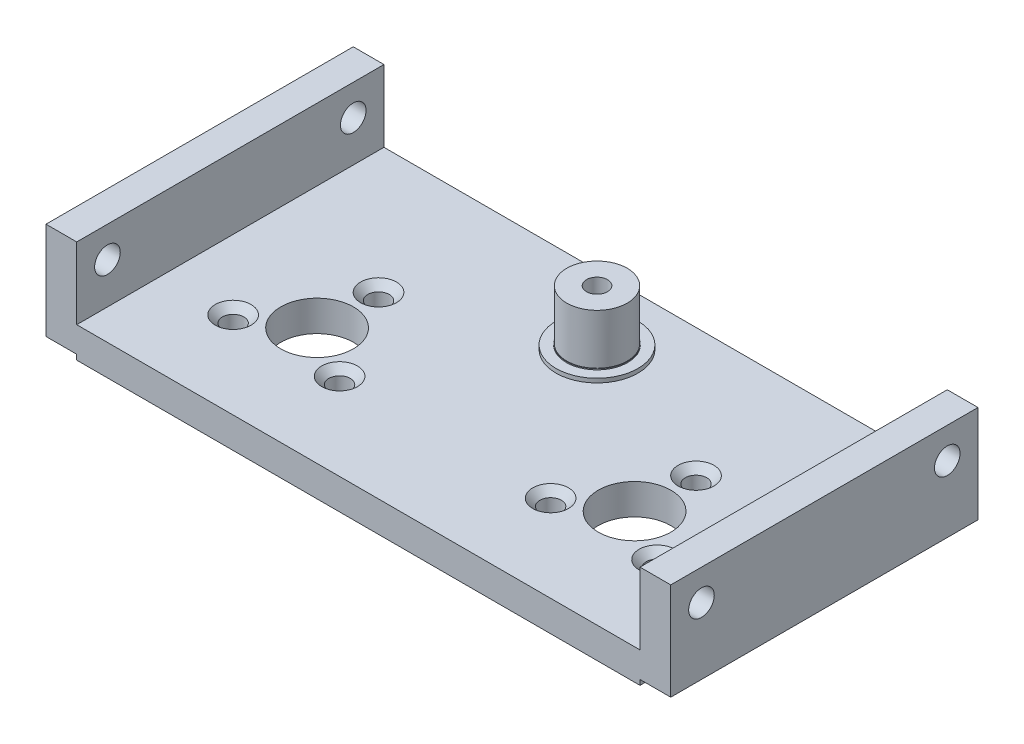
SolidWorks part; units mm, degrees
material "6061 Alloy"
ref_plane "Front Plane" through (0, 0, 0) normal (0, 0, 1) x (1, 0, 0)
ref_plane "Top Plane" through (0, 0, 0) normal (0, 1, 0) x (1, 0, 0)
ref_plane "Right Plane" through (0, 0, 0) normal (1, 0, 0) x (0, 0, -1)
sketch "Sketch1" plane through (0, 0, 0) normal (0, 1, 0) x (1, 0, 0)
  line L0 (55, 1) -> (0, 1)
  line L2 (0, 1) -> (0, 31)
  line L3 (0, 31) -> (55, 31)
  line L4 (55, 1) -> (55, 31)
  dimension "D1" = 30
extrude "Boss-Extrude1" add sketch "Sketch1" along normal blind 3
sketch "Sketch2" plane through (0, 3, 0) normal (0, 1, 0) x (1, 0, 0)
  line L0 (0, 1) -> (55, 1) construction
  circle A0 centre (27.5, 24.3) radius 2.95
  dimension "D1" = 5.9
  dimension "D2" = 23.3
extrude "Boss-Extrude2" add sketch "Sketch2" along normal blind 4.9
sketch "Sketch8" plane through (0, 3, 0) normal (0, 1, 0) x (1, 0, 0)
  line L0 (55, 1) -> (55, 31) construction
  circle A1 centre (43, 12.4678) radius 3.55
  circle A3 centre (27.5, 24.3) radius 2.95 construction
  point P0 (43, 12.4678)
  dimension "D3" = 7.1
  dimension "D1" = 19.5
  dimension "D2" = 12
extrude "Cut-Extrude2" cut sketch "Sketch8" against normal blind 6
ref_plane "Plane1" through (27.5, 0, 0) normal (1, 0, 0) x (0, 0, -1)
mirror "Mirror1" about plane through (27.5, 0, 0) normal (1, 0, 0) of "Cut-Extrude2"
sketch "Sketch10" plane through (0, 3, 0) normal (0, 1, 0) x (1, 0, 0)
  line L0 (55, 1) -> (58, 1)
  line L1 (55, 31) -> (58, 31)
  line L2 (55, 31) -> (55, 1)
  line L4 (58, 31) -> (58, 1)
extrude "Boss-Extrude3" add sketch "Sketch10" along normal blind 6.5 and the other way blind 3
sketch "Sketch11" plane through (0, 3, 0) normal (0, 1, 0) x (1, 0, 0)
  line L0 (0, 1) -> (-3, 1)
  line L1 (0, 31) -> (-3, 31)
  line L2 (0, 31) -> (0, 1)
  line L4 (-3, 31) -> (-3, 1)
extrude "Boss-Extrude4" add sketch "Sketch11" along normal blind 6.5 and the other way blind 3
hole_wizard "Tap Drill for M3x0.5 Tap1" positions "Sketch13" profile "Sketch12" hole size "M3x0.5" standard "ANSI Metric"
sketch "Sketch13" plane through (-3, 0, 0) normal (-1, 0, 0) x (0, 0, 1)
  line L2 (-1, 0) -> (-1, 9.5) construction
  line L3 (-31, 0) -> (-31, 9.5) construction
  line L4 (-31, 9.5) -> (-1, 9.5) construction
  point P0 (-28, 6.5)
  point P2 (-4, 6.5)
  dimension "D1" = 3
  dimension "D2" = 3
  dimension "D3" = 3
  dimension "D4" = 3
sketch "Sketch12" plane through (-3, 6.5, -28) normal (0, 1, 0) x (0, 0, 1)
  line L0 (0, 0) -> (0, 10.7511)
  line L1 (0, 10.7511) -> (1.25, 10)
  line L2 (1.25, 10) -> (1.25, 0)
  line L5 (1.25, 0) -> (0, 0)
  line L10 (0, 10.7511) -> (-1.25, 10) construction
  line L11 (0, -6.35) -> (0, 107.95) construction
  dimension "Hole Dia." = 2.5
  dimension "Hole Depth" = 10
  dimension "Drill Angle" = 118
mirror "Mirror2" about plane through (27.5, 0, 0) normal (1, 0, 0) of "Tap Drill for M3x0.5 Tap1"
sketch "Sketch15" plane through (0, 7.9, 0) normal (0, 1, 0) x (1, 0, 0)
  point P0 (27.5, 24.3)
hole_wizard "Tap Drill for M2.5x0.45 Tap2" positions "Sketch17" profile "Sketch16" hole size "M2.5x0.45" standard "ANSI Metric"
sketch "Sketch17" plane through (0, 7.9, 0) normal (0, 1, 0) x (1, 0, 0)
  point P0 (27.5, 24.3)
sketch "Sketch16" plane through (27.5, 7.9, -24.3) normal (1, 0, 0) x (0, 0, 1)
  line L0 (0, 0) -> (0, 6.6159)
  line L1 (0, 6.6159) -> (1.025, 6)
  line L2 (1.025, 6) -> (1.025, 0)
  line L5 (1.025, 0) -> (0, 0)
  line L10 (0, 6.6159) -> (-1.025, 6) construction
  line L11 (0, -6.35) -> (0, 107.95) construction
  dimension "Hole Dia." = 2.05
  dimension "Hole Depth" = 6
  dimension "Drill Angle" = 118
sketch "Sketch18" plane through (0, 3, 0) normal (0, 1, 0) x (1, 0, 0)
  circle A0 centre (12, 18.4678) radius 1.05
  circle A1 centre (43, 18.4678) radius 1.05
  circle A2 centre (12, 12.4678) radius 3.55 construction
  circle A3 centre (43, 12.4678) radius 3.55 construction
  dimension "D1" = 2.1
  dimension "D2" = 2.1
  dimension "D3" = 6
  dimension "D4" = 6
extrude "Cut-Extrude4" cut sketch "Sketch18" against normal blind 10 contours A0
pattern_circular "CirPattern2" count 3 over 360 about axis through (12, -3, -12.4678) along (0, 1, 0) of "Cut-Extrude4"
mirror "Mirror3" about plane through (27.5, 0, 0) normal (1, 0, 0) of "CirPattern2", "Cut-Extrude4"
sketch "Sketch21" plane through (0, 3, 0) normal (0, 1, 0) x (1, 0, 0)
  line L1 (55, 31) -> (0, 31)
  line L2 (55, 31) -> (55, 1)
  line L3 (55, 1) -> (0, 1)
  line L4 (0, 31) -> (0, 1)
  circle A0 centre (27.5, 24.3) radius 4
extrude "Cut-Extrude7" cut sketch "Sketch21" against normal blind 0.5
sketch "Sketch23" plane through (0, 3, 0) normal (0, 1, 0) x (1, 0, 0)
  circle A0 centre (27.5, 24.3) radius 4
  circle A1 centre (27.5, 24.3) radius 3
extrude "Cut-Extrude8" cut sketch "Sketch23" against normal blind 0.1
hole_wizard "CSK for M2 Flat Head Machine Screw1" positions "3DSketch1" profile "Sketch24" countersink size "M2" standard "ANSI Metric"
sketch3d "3DSketch1"
  line L0 (43, 0, -18.4678) -> (43, 2.5, -18.4678) construction
  line L1 (48.1962, 0, -9.4678) -> (48.1962, 2.5, -9.4678) construction
  line L2 (37.8038, 0, -9.4678) -> (37.8038, 2.5, -9.4678) construction
  line L3 (17.1962, 0, -9.4678) -> (17.1962, 2.5, -9.4678) construction
  line L4 (12, 0, -18.4678) -> (12, 2.5, -18.4678) construction
  line L5 (6.8038, 0, -9.4678) -> (6.8038, 2.5, -9.4678) construction
  point P0 (43, 2.5, -18.4678)
  point P4 (48.1962, 2.5, -9.4678)
  point P8 (37.8038, 2.5, -9.4678)
  point P12 (17.1962, 2.5, -9.4678)
  point P16 (12, 2.5, -18.4678)
  point P20 (6.8038, 2.5, -9.4678)
sketch "Sketch24" plane through (43, 2.5, -18.4678) normal (1, 0, 0) x (0, 0, 1)
  line L0 (0, 0) -> (0, 10.1309)
  line L1 (0, 10.1309) -> (1.05, 9.5)
  line L2 (1.05, 9.5) -> (1.05, 0.7)
  line L3 (1.05, 0.7) -> (1.75, 0)
  line L5 (1.75, 0) -> (0, 0)
  line L6 (-1.05, 0.7) -> (-1.75, 0) construction
  line L10 (0, 10.1309) -> (-1.05, 9.5) construction
  line L11 (0, -6.35) -> (0, 107.95) construction
  dimension "Hole Dia." = 2.1
  dimension "Hole Depth" = 9.5
  dimension "Near C'Sink Dia." = 3.5
  dimension "Near C'Sink Angle" = 90
  dimension "Drill Angle" = 118
sketch "Sketch25" plane through (0, 0, 0) normal (0, -1, 0) x (-1, 0, 0)
  line L1 (-55, 1) -> (0, 1)
  line L2 (-55, 1) -> (-55, 31)
  line L3 (-55, 31) -> (0, 31)
  line L4 (0, 1) -> (0, 31)
  circle A0 centre (-43, 12.4678) radius 3.55
  circle A1 centre (-48.1962, 9.4678) radius 1.05
  circle A2 centre (-43, 18.4678) radius 1.05
  circle A3 centre (-37.8038, 9.4678) radius 1.05
  circle A4 centre (-12, 12.4678) radius 3.55
  circle A5 centre (-17.1962, 9.4678) radius 1.05
  circle A6 centre (-12, 18.4678) radius 1.05
  circle A7 centre (-6.8038, 9.4678) radius 1.05
extrude "Boss-Extrude6" add sketch "Sketch25" along normal blind 0.5
